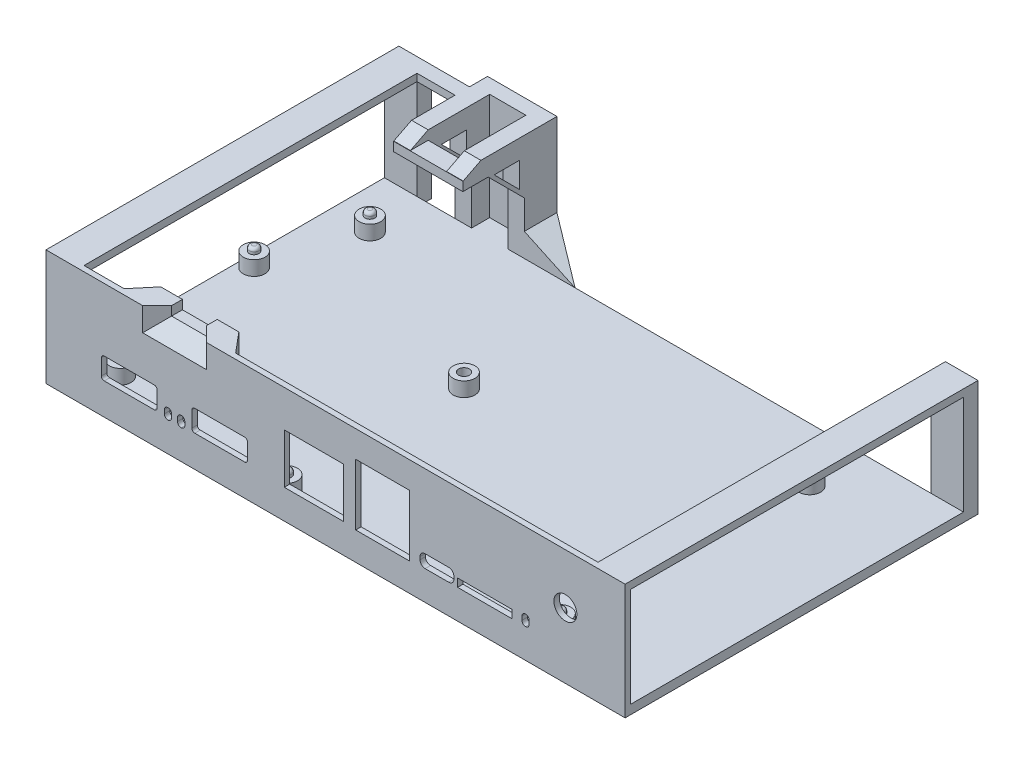
SolidWorks part; units mm, degrees
ref_plane "Front Plane" through (0, 0, 0) normal (0, 0, 1) x (1, 0, 0)
ref_plane "Top Plane" through (0, 0, 0) normal (0, 1, 0) x (1, 0, 0)
ref_plane "Right Plane" through (0, 0, 0) normal (1, 0, 0) x (0, 0, -1)
sketch "Sketch1" plane through (0, 0, 0) normal (0, 1, 0) x (1, 0, 0)
  line L0 (34.5, 92) -> (160, 92)
  line L1 (0, 0) -> (160, 0)
  line L2 (0, 0) -> (0, 92)
  line L3 (0, 92) -> (24, 92)
  line L4 (160, 0) -> (160, 92)
  line L6 (24, 92) -> (24, 99)
  line L7 (24, 99) -> (34.5, 99)
  line L8 (34.5, 92) -> (34.5, 99)
  dimension "D1" = 160
  dimension "D2" = 92
  dimension "D3" = 7
  dimension "D4" = 10.5
  dimension "D5" = 24
extrude "Boss-Extrude1" add sketch "Sketch1" along normal blind 2.5
sketch "Sketch3" plane through (0, 0, 0) normal (0, 1, 0) x (1, 0, 0)
  line L1 (0, 0) -> (160, 0)
  line L2 (0, 0) -> (0, -1.5)
  line L3 (0, -1.5) -> (160, -1.5)
  line L4 (160, 0) -> (160, -1.5)
  dimension "D1" = 1.5
  dimension "D2" = 160
extrude "Boss-Extrude2" add sketch "Sketch3" along normal blind 32
sketch "Sketch4" plane through (0, 2.5, 0) normal (0, 1, 0) x (1, 0, 0)
  line L0 (160, 0) -> (0, 0) construction
  line L1 (0, 92) -> (0, 0) construction
  line L2 (0, 0) -> (160, 0) construction
  circle A0 centre (11, 8) radius 3
  circle A1 centre (11, 77) radius 3
  circle A2 centre (61.5, 3.5) radius 3
  circle A3 centre (132.5, 8) radius 3
  circle A4 centre (132.5, 77) radius 3
  circle A5 centre (3.5, 52.5) radius 3
  circle A6 centre (61.5, 52.5) radius 3
  dimension "D1" = 8
  dimension "D3" = 77
  dimension "D4" = 61.5
  dimension "D5" = 132.5
  dimension "D6" = 52.5
  dimension "D8" = 3.5
  dimension "D2" = 11
  dimension "D7" = 3.5
extrude "Boss-Extrude3" add sketch "Sketch4" along normal blind 4
sketch "Sketch6" plane through (0, 6.5, 0) normal (0, 1, 0) x (1, 0, 0)
  circle A0 centre (11, 77) radius 1.33
  circle A1 centre (3.5, 52.5) radius 1.33
  circle A2 centre (11, 8) radius 1.33
  circle A3 centre (61.5, 3.5) radius 1.33
  circle A4 centre (132.5, 8) radius 1.33
  circle A5 centre (132.5, 77) radius 1.33
extrude "Boss-Extrude5" add sketch "Sketch6" along normal blind 1.5
sketch "Sketch7" plane through (0, 6.5, 0) normal (0, 1, 0) x (1, 0, 0)
  circle A0 centre (61.5, 52.5) radius 1.5
extrude "Cut-Extrude1" cut sketch "Sketch7" against normal blind 4
sketch "Sketch8" plane through (0, 0, 0) normal (0, 1, 0) x (1, 0, 0)
  line L0 (24, 92) -> (0, 92) construction
  line L1 (19.5, 92) -> (24.0826, 92)
  line L2 (19.5, 92) -> (19.5, 99)
  line L4 (24.0826, 92) -> (24.0826, 97)
  line L6 (34.0826, 92) -> (38.6652, 92)
  line L7 (34.0826, 92) -> (34.0826, 97)
  line L9 (38.6652, 92) -> (38.6652, 99)
  line L10 (24.0826, 97) -> (34.0826, 97)
  line L11 (19.5, 99) -> (19.5, 101)
  line L12 (19.5, 101) -> (38.6652, 101)
  line L13 (38.6652, 99) -> (38.6652, 101)
  dimension "D1" = 19.5
  dimension "D2" = 5
  dimension "D3" = 5
  dimension "D4" = 10
  dimension "D5" = 7
  dimension "D6" = 7
  dimension "D7" = 2
extrude "Boss-Extrude6" add sketch "Sketch8" along normal blind 32
sketch "Sketch10" plane through (0, 0, 0) normal (0, 1, 0) x (1, 0, 0)
  line L6 (38.6652, 101) -> (38.6652, 92)
  line L7 (38.6652, 92) -> (52.6652, 92)
  line L8 (160, 92) -> (38.6652, 92) construction
  line L9 (52.6652, 92) -> (38.6652, 101)
  dimension "D2" = 14
extrude "Boss-Extrude7" add sketch "Sketch10" along normal blind 2.5
chamfer "Chamfer2" distance 6.5 angle 65 1 edges at (38.6652, 2.5, -96.5) first distance on face at (38.6652, 17.25, -96.5)
sketch "Sketch11" plane through (0, 0, 1.5) normal (0, 0, 1) x (1, 0, 0)
  line L0 (0, 0) -> (160, 0) construction
  line L1 (15.3, 14.63) -> (30.7, 14.63)
  line L2 (15.3, 14.63) -> (15.3, 8.68)
  line L3 (15.3, 8.68) -> (30.7, 8.68)
  line L4 (30.7, 14.63) -> (30.7, 8.68)
  line L5 (0, 32) -> (0, 0) construction
  line L6 (0, 32) -> (160, 32) construction
  line L7 (40.3, 8.68) -> (55.7, 8.68)
  line L8 (40.3, 8.68) -> (40.3, 14.63)
  line L9 (40.3, 14.63) -> (55.7, 14.63)
  line L10 (55.7, 8.68) -> (55.7, 14.63)
  line L11 (65.84, 8.1) -> (82.17, 8.1)
  line L12 (65.84, 8.1) -> (65.84, 21.84)
  line L13 (65.84, 21.84) -> (82.17, 21.84)
  line L14 (82.17, 8.1) -> (82.17, 21.84)
  line L15 (85.56, 7.75) -> (100.46, 7.75)
  line L16 (85.56, 7.75) -> (85.56, 24.67)
  line L17 (85.56, 24.67) -> (100.46, 24.67)
  line L18 (100.46, 7.75) -> (100.46, 24.67)
  line L19 (103.34, 11.66) -> (112.68, 11.66)
  line L20 (103.34, 11.66) -> (103.34, 8.1)
  line L21 (103.34, 8.1) -> (112.68, 8.1)
  line L22 (112.68, 11.66) -> (112.68, 8.1)
  line L23 (113.71, 10.35) -> (128.81, 10.35)
  line L24 (113.71, 10.35) -> (113.71, 8.1)
  line L25 (113.71, 8.1) -> (128.81, 8.1)
  line L26 (128.81, 10.35) -> (128.81, 8.1)
  line L27 (32.7, 8.1) -> (34.7, 8.1)
  line L28 (32.7, 8.1) -> (32.7, 11.1)
  line L29 (32.7, 11.1) -> (34.7, 11.1)
  line L30 (34.7, 8.1) -> (34.7, 11.1)
  line L31 (36.35, 8.1) -> (38.35, 8.1)
  line L32 (36.35, 8.1) -> (36.35, 11.1)
  line L33 (36.35, 11.1) -> (38.35, 11.1)
  line L34 (38.35, 8.1) -> (38.35, 11.1)
  line L35 (131.5, 8.1) -> (133.5, 8.1)
  line L36 (131.5, 8.1) -> (131.5, 11.1)
  line L37 (131.5, 11.1) -> (133.5, 11.1)
  line L38 (133.5, 8.1) -> (133.5, 11.1)
  line L39 (30.7, 32) -> (40.3, 32)
  line L40 (30.7, 32) -> (30.7, 29.5)
  line L41 (30.7, 29.5) -> (40.3, 29.5)
  line L42 (40.3, 32) -> (40.3, 29.5)
  circle A0 centre (143.5, 18.1) radius 3.175
  dimension "D39" = 6.35
  dimension "D1" = 15.4
  dimension "D2" = 5.95
  dimension "D3" = 8.68
  dimension "D4" = 15.3
  dimension "D5" = 9.6
  dimension "D6" = 5.95
  dimension "D7" = 15.4
  dimension "D8" = 8.68
  dimension "D9" = 16.33
  dimension "D10" = 13.74
  dimension "D11" = 8.1
  dimension "D12" = 10.14
  dimension "D13" = 3.39
  dimension "D14" = 16.92
  dimension "D15" = 14.9
  dimension "D16" = 7.75
  dimension "D17" = 3.56
  dimension "D18" = 9.34
  dimension "D19" = 2.88
  dimension "D20" = 8.1
  dimension "D21" = 1.03
  dimension "D22" = 15.1
  dimension "D23" = 2.25
  dimension "D24" = 8.1
  dimension "D25" = 2
  dimension "D26" = 3
  dimension "D27" = 8.1
  dimension "D28" = 32.7
  dimension "D29" = 2
  dimension "D30" = 3
  dimension "D31" = 8.1
  dimension "D32" = 1.65
  dimension "D33" = 2
  dimension "D34" = 3
  dimension "D35" = 131.5
  dimension "D36" = 9.6
  dimension "D37" = 15.4
  dimension "D38" = 2.5
  dimension "D40" = 10
  dimension "D41" = 10
extrude "Cut-Extrude2" cut sketch "Sketch11" against normal up to next
fillet "Fillet1" radius 1.4 4 edges at (103.34, 8.1, 0.75) (103.34, 11.66, 0.75) (112.68, 11.66, 0.75) (112.68, 8.1, 0.75)
fillet "Fillet2" radius 0.8 8 edges at (30.7, 14.63, 0.75) (30.7, 8.68, 0.75) (15.3, 8.68, 0.75) (15.3, 14.63, 0.75) (40.3, 8.68, 0.75) (40.3, 14.63, 0.75) (55.7, 8.68, 0.75) (55.7, 14.63, 0.75)
fillet "Fillet3" radius 0.8 6 edges at (132.5, 8, -6.67) (132.5, 8, -75.67) (11, 8, -75.67) (3.5, 8, -51.17) (61.5, 8, -2.17) (11, 8, -6.67)
fillet "Fillet4" radius 1 12 edges at (34.7, 8.1, 0.75) (38.35, 8.1, 0.75) (38.35, 11.1, 0.75) (34.7, 11.1, 0.75) (32.7, 8.1, 0.75) (36.35, 8.1, 0.75) (36.35, 11.1, 0.75) (32.7, 11.1, 0.75) (131.5, 11.1, 0.75) (133.5, 11.1, 0.75) (131.5, 8.1, 0.75) (133.5, 8.1, 0.75)
sketch "Sketch12" plane through (0, 0, 0) normal (0, 0, -1) x (-1, 0, 0)
  line L0 (-160, 32) -> (-40.3, 32) construction
  line L1 (-40.3, 29.5) -> (-30.7, 29.5)
  line L3 (-40.3, 26.5) -> (-30.7, 26.5)
  line L5 (-40.3, 26.5) -> (-46.3, 26.5)
  line L6 (-40.3, 29.5) -> (-40.3, 32)
  line L7 (-40.3, 32) -> (-46.3, 32)
  line L8 (-46.3, 26.5) -> (-46.3, 32)
  line L9 (-30.7, 32) -> (0, 32) construction
  line L10 (-30.7, 26.5) -> (-24.7, 26.5)
  line L11 (-30.7, 29.5) -> (-30.7, 32)
  line L12 (-30.7, 32) -> (-24.7, 32)
  line L13 (-24.7, 26.5) -> (-24.7, 32)
  dimension "D1" = 9.6
  dimension "D2" = 3
  dimension "D3" = 6
  dimension "D4" = 6
extrude "Boss-Extrude8" add sketch "Sketch12" along normal blind 5.5
chamfer "Chamfer3" distance 5.5 angle 45 1 edges at (35.5, 26.5, 0)
chamfer "Chamfer4" distance 4.6 angle 50 2 edges at (46.3, 26.5, 0) (24.7, 26.5, 0) first distance on face at (23, 11.655, 0)
chamfer "Chamfer5" distance 4 angle 45 3 edges at (40.3, 30.75, 1.5) (35.5, 29.5, 1.5) (30.7, 30.75, 1.5)
sketch "Sketch13" plane through (0, 32, 0) normal (0, 1, 0) x (1, 0, 0)
  line L5 (19.5, 92) -> (24.0826, 92)
  line L6 (19.5, 92) -> (19.5, 80)
  line L7 (19.5, 80) -> (24.0826, 80)
  line L8 (24.0826, 92) -> (24.0826, 80)
  line L13 (34.0826, 92) -> (38.6652, 92)
  line L14 (34.0826, 92) -> (34.0826, 80)
  line L15 (34.0826, 80) -> (38.6652, 80)
  line L16 (38.6652, 92) -> (38.6652, 80)
  dimension "D1" = 12
  dimension "D2" = 4.5826
  dimension "D3" = 4.5826
  dimension "D4" = 12
extrude "Boss-Extrude9" add sketch "Sketch13" against normal blind 5
sketch "Sketch16" plane through (0, 0, -80) normal (0, 0, 1) x (1, 0, 0)
  line L1 (19.5, 27) -> (38.6652, 27)
  line L2 (19.5, 27) -> (19.5, 29.5)
  line L3 (19.5, 29.5) -> (38.6652, 29.5)
  line L4 (38.6652, 27) -> (38.6652, 29.5)
  dimension "D1" = 2.5
extrude "Boss-Extrude10" add sketch "Sketch16" along normal blind 5
chamfer "Chamfer6" distance 2.5 angle 63 2 edges at (21.7913, 29.5, -80) (36.3739, 29.5, -80) first distance on face at (21.7913, 30.75, -80) first distance on face at (36.3739, 30.75, -80)
chamfer "Chamfer7" distance 10 angle 45 2 edges at (21.7913, 27, -92) (36.3739, 27, -92)
sketch "Sketch17" plane through (19.5, 0, 0) normal (-1, 0, 0) x (0, 0, 1)
  line L0 (-90.6584, 19.6833) -> (-90.6584, 26.6833)
  line L1 (-90.6584, 26.6833) -> (-83.6584, 26.6833)
  line L2 (-83.6584, 26.6833) -> (-90.6584, 19.6833)
  dimension "D1" = 7
  dimension "D2" = 7
  dimension "D3" = 3
extrude "Cut-Extrude3" cut sketch "Sketch17" against normal blind 20
sketch "Sketch18" plane through (0, 0, 0) normal (0, 1, 0) x (1, 0, 0)
  line L1 (0, 92) -> (9, 92)
  line L2 (0, 92) -> (0, 96)
  line L3 (0, 96) -> (9, 96)
  line L4 (9, 92) -> (9, 96)
  line L5 (160, 92) -> (151, 92)
  line L6 (160, 92) -> (160, 96)
  line L7 (160, 96) -> (151, 96)
  line L8 (151, 92) -> (151, 96)
  dimension "D1" = 9
  dimension "D2" = 4
  dimension "D3" = 9
  dimension "D4" = 4
extrude "Boss-Extrude11" add sketch "Sketch18" along normal blind 30
sketch "Sketch19" plane through (0, 30, 0) normal (0, 1, 0) x (1, 0, 0)
  line L0 (0, 0) -> (160, 0) construction
  line L1 (0, 96) -> (9, 96)
  line L2 (0, 96) -> (0, 0)
  line L3 (0, 0) -> (9, 0)
  line L4 (9, 92) -> (9, 0)
  line L5 (19.5, 101) -> (19.5, 80) construction
  line L6 (151, 96) -> (160, 96)
  line L7 (151, 96) -> (151, 0)
  line L8 (151, 0) -> (160, 0)
  line L9 (160, 96) -> (160, 0)
  line L10 (9, 96) -> (19.5, 96)
  line L12 (9, 92) -> (19.5, 92)
  line L13 (19.5, 96) -> (19.5, 92)
  line L14 (19.5, 92) -> (9, 92) construction
  dimension "D1" = 9
extrude "Boss-Extrude12" add sketch "Sketch19" along normal blind 2
